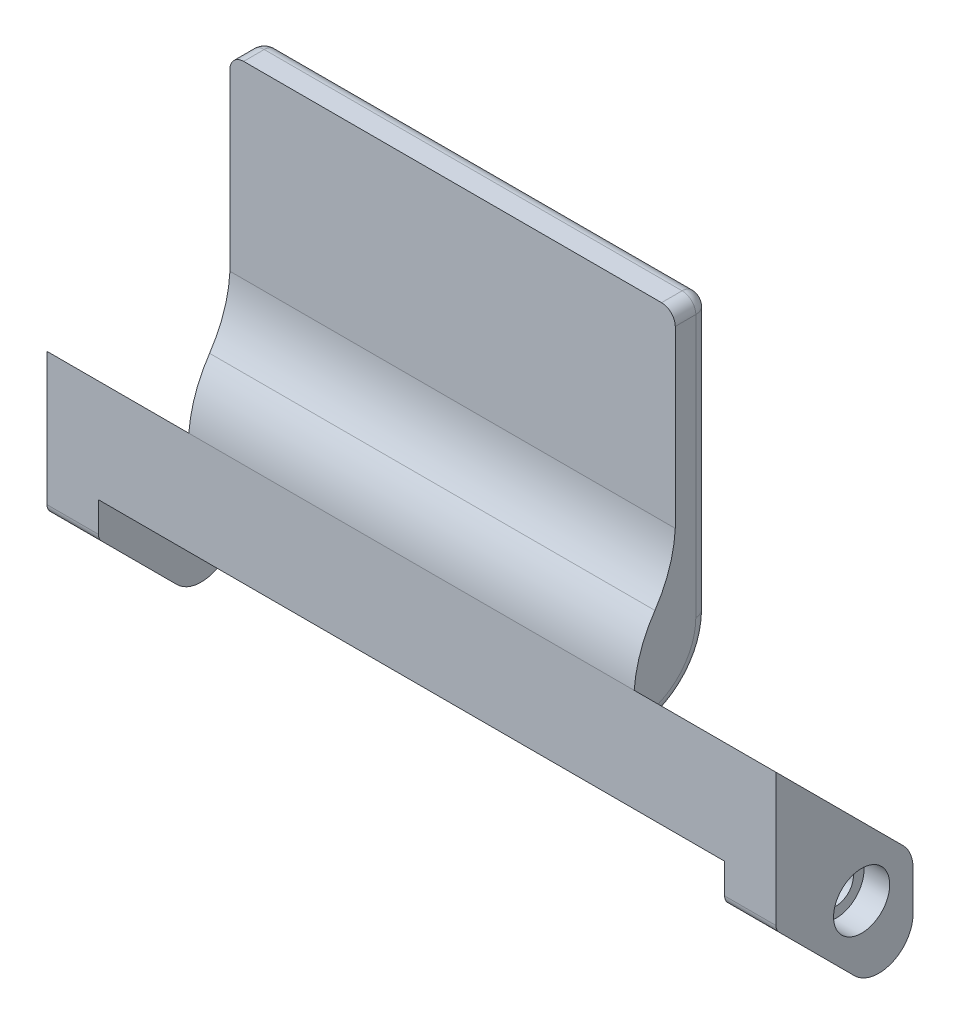
SolidWorks part; units mm, degrees
note: The reader was unsure of these and kept them because the rebuilt part matched: shared geometry of "Sketch8<3>".
ref_plane "Front Plane" through (0, 0, 0) normal (0, 0, 1) x (1, 0, 0)
ref_plane "Top Plane" through (0, 0, 0) normal (0, 1, 0) x (1, 0, 0)
ref_plane "Right Plane" through (0, 0, 0) normal (1, 0, 0) x (0, 0, -1)
ref_plane "Plane1" through (-53.2, 0, 0) normal (1, 0, 0) x (0, 0, -1)
sketch "Sketch1" plane through (0, 0, 0) normal (0, 0, 1) x (1, 0, 0)
  line L1 (32.5, -32.5) -> (-32.5, -32.5)
  line L2 (32.5, -32.5) -> (32.5, 32.5)
  line L3 (32.5, 32.5) -> (-32.5, 32.5)
  line L4 (-32.5, -32.5) -> (-32.5, 32.5)
  line L5 (32.5, -32.5) -> (-32.5, 32.5) construction
  line L6 (32.5, 32.5) -> (-32.5, -32.5) construction
  point P0 (0, 0)
  dimension "D1" = 65
  dimension "D2" = 65
extrude "Boss-Extrude1" add sketch "Sketch1" along normal blind 5
sketch "Sketch2" plane through (-53.2, 12.6, 0) normal (1, 0, 0) x (0, 1, 0)
  line L0 (-65.6, 5) -> (-65.6, -10)
  line L1 (-65.6, -10) -> (-58.1, -10)
  line L2 (-65.6, 5) -> (-45.1, 5)
  line L4 (-58.1, -10) -> (-58.1, 0)
  line L5 (-58.1, 0) -> (-45.1, 0)
  line L6 (-45.1, 0) -> (-45.1, 5)
  dimension "D1" = 15
  dimension "D2" = 45.5
  dimension "D3" = 7.5
sketch "Sketch4" plane through (-53.2, 0, 0) normal (-1, 0, 0) x (0, 0, 1)
  line L0 (5, -12.5) -> (-15, -32.5)
  line L1 (5, 32.5) -> (5, -32.5) construction
  line L2 (-15, -32.5) -> (-15, -52.5)
  line L3 (-15, -52.5) -> (5, -32.5)
  line L4 (0, -32.5) -> (5, -32.5) construction
  line L5 (5, -32.5) -> (5, -12.5)
  dimension "D1" = 45
  dimension "D2" = 20
  dimension "D3" = 20
extrude "Boss-Extrude3" add sketch "Sketch4" against normal blind 7.5
sketch "Sketch7" plane through (-53.2, 0, 0) normal (1, 0, 0) x (0, 0, -1)
  line L0 (-5, -32.5) -> (0, -32.5)
  line L1 (0, -32.5) -> (0, -17.5)
  line L2 (0, -32.5) -> (0, 32.5) construction
  line L3 (-5, -12.5) -> (15, -32.5) construction
  line L4 (0, -17.5) -> (-5, -12.5)
  line L5 (-5, -32.5) -> (-5, 32.5) construction
  line L6 (-5, -12.5) -> (-5, -32.5)
extrude "Boss-Extrude5" add sketch "Sketch7" along normal up to surface (85.7 mm away)
sketch "Sketch8" plane through (-53.2, 0, 0) normal (-1, 0, 0) x (0, 0, 1)
  line L0 (-15, -42.5) -> (5, -22.5) construction
  line L1 (-15, -32.5) -> (-15, -52.5) construction
  line L2 (5, -12.5) -> (5, -32.5) construction
  line L3 (-7.5, -35) -> (-15, -35) construction
  circle A0 centre (-7.5, -35) radius 2.55
  circle A1 centre (-7.5, -35) radius 4.1
  dimension "D1" = 5.1
  dimension "D2" = 8.2
  dimension "D3" = 7.5
extrude "Cut-Extrude4" cut sketch "Sketch8" against normal through all contours A0
extrude "Cut-Extrude5" cut sketch "Sketch8<3>" against normal blind 3.75
sketch "Sketch8<3>" plane through (-53.2, 0, 0) normal (-1, 0, 0) x (0, 0, 1) same geometry as "Sketch8"
mirror "Mirror5" about plane through (0, 0, 0) normal (1, 0, 0) of "Boss-Extrude3", "Boss-Extrude5"
sketch "Sketch9" plane through (53.2, 0, 0) normal (1, 0, 0) x (0, 0, -1)
  line L0 (0, -17.5) -> (-5, -12.5)
  line L1 (-5, -12.5) -> (-5, -32.5)
  line L5 (0, -17.5) -> (0, -32.5)
  line L6 (0, -32.5) -> (-5, -32.5)
  line L7 (-5, -32.5) -> (15, -52.5)
  line L8 (15, -52.5) -> (15, -32.5)
  line L9 (15, -32.5) -> (0, -17.5)
  line L12 (-5, -32.5) -> (15, -52.5)
  line L13 (15, -52.5) -> (15, -32.5)
  line L14 (15, -32.5) -> (0, -17.5)
  circle A0 centre (7.5, -35) radius 2.55
  dimension "D2" = 5.1
  dimension "D1" = 0
extrude "Boss-Extrude6" add sketch "Sketch9" against normal blind 7.5
sketch "Sketch10" plane through (53.2, 0, 0) normal (1, 0, 0) x (0, 0, -1)
  circle A0 centre (7.5, -35) radius 4.1
  dimension "D1" = 8.2
extrude "Cut-Extrude6" cut sketch "Sketch10" against normal blind 3.75
sketch "Sketch11" plane through (0, 0, 0) normal (1, 0, 0) x (0, 0, -1)
  line L0 (-5, -12.5) -> (-5, -32.5)
  line L1 (1, 4.9672) -> (1, 32.5)
  line L2 (1, 32.5) -> (6, 32.5)
  line L3 (6, 32.5) -> (6, 6.0076)
  line L5 (-5, 32.5) -> (0, 32.5) construction
  line L6 (-5, -32.5) -> (0, -32.5)
  line L7 (0, -32.5) -> (0, -17.5)
  line L8 (0, -17.5) -> (0, 32.5) construction
  arc A0 (1, 4.9672) -> (-1.9708, -3.9155) centre (-16.2173, 5.7874) cw
  arc A1 (-1.9708, -3.9155) -> (-5, -12.5) centre (12.7356, -13.9316) ccw
  arc A2 (6, 6.0076) -> (3.482, -5.2726) centre (-20.5257, 6.0076) cw
  arc A3 (3.482, -5.2726) -> (0, -17.5) centre (39.1922, -22.0513) ccw
  dimension "D2" = 17.2368
  dimension "D3" = 17.7933
  dimension "D4" = 26.5257
  dimension "D5" = 39.4555
  dimension "D1" = 5
  dimension "D6" = 8.5845
  dimension "D7" = 17.4672
  dimension "D8" = 12.2274
  dimension "D9" = 1
extrude "Boss-Extrude7" add sketch "Sketch11" along normal mid plane 65
sketch "Sketch13" plane through (0, 0, 0) normal (1, 0, 0) x (0, 0, -1)
  line L0 (1, 32.5) -> (-5, 32.5)
  line L1 (-5, 32.5) -> (-5, -12.5)
  line L6 (-5, -32.5) -> (0, -32.5)
  line L7 (0, -32.5) -> (0, -17.5)
  line L8 (6, 6.0076) -> (6, 32.5)
  line L9 (6, 32.5) -> (1, 32.5)
  line L10 (1, 32.5) -> (1, 4.9672)
  line L11 (-5, -12.5) -> (-5, -32.5)
  line L12 (-5, -32.5) -> (0, -32.5)
  line L13 (0, -32.5) -> (0, -17.5)
  line L14 (6, 6.0076) -> (6, 32.5)
  line L15 (6, 32.5) -> (1, 32.5)
  line L16 (1, 32.5) -> (1, 4.9672)
  line L17 (-5, -12.5) -> (-5, -32.5)
  arc A4 (3.482, -5.2726) -> (0, -17.5) centre (39.1922, -22.0513) ccw
  arc A5 (3.482, -5.2726) -> (6, 6.0076) centre (-20.5257, 6.0076) ccw
  arc A6 (-1.9708, -3.9155) -> (1, 4.9672) centre (-16.2173, 5.7874) ccw
  arc A7 (-1.9708, -3.9155) -> (-5, -12.5) centre (12.7356, -13.9316) ccw
  arc A8 (3.482, -5.2726) -> (0, -17.5) centre (39.1922, -22.0513) ccw
  arc A9 (3.482, -5.2726) -> (6, 6.0076) centre (-20.5257, 6.0076) ccw
  arc A10 (-1.9708, -3.9155) -> (1, 4.9672) centre (-16.2173, 5.7874) ccw
  arc A11 (-1.9708, -3.9155) -> (-5, -12.5) centre (12.7356, -13.9316) ccw
  dimension "D1" = 0
extrude "Cut-Extrude7" cut sketch "Sketch13" against normal mid plane 65 contours A11 A10 L16 L0 L1
fillet "Fillet1" radius 5 4 edges at (-49.45, -32.5, -15) (49.45, -32.5, -15) (-49.45, -52.5, -15) (49.45, -52.5, -15)
sketch "Sketch14" plane through (0, 0, 5) normal (0, 0, 1) x (1, 0, 0)
  line L1 (-45.7, -32.5) -> (45.7, -32.5) construction
  line L3 (0, 0) -> (0, -32.5) construction
  line L5 (-45.7, -32.5) -> (-45.7, -27.5)
  line L6 (-45.7, -27.5) -> (45.7, -27.5)
  line L7 (45.7, -27.5) -> (45.7, -32.5)
  line L8 (-45.7, -32.5) -> (45.7, -32.5)
  point P1 (2.3917, -32.5)
  point P6 (73.7438, -32.5)
  dimension "D1" = 5
extrude "Cut-Extrude8" cut sketch "Sketch14" against normal blind 10
fillet "Fillet2" radius 1.5 3 edges at (49.45, -32.5, 5) (-49.45, -32.5, 5) (0, -27.5, 0)
fillet "Fillet7" radius 2 2 edges at (-32.5, 32.5, -3.5) (32.5, 32.5, -3.5)
sketch "Sketch16" plane through (-32.5, 0, 0) normal (-1, 0, 0) x (0, 0, 1)
  line L0 (-6, 6.0076) -> (-6, -7.8214)
  line L1 (-6, 6.0076) -> (-6, 30.5) construction
  line L2 (-6, 6.0076) -> (-3.1128, 6.0076)
  line L3 (-3.1128, 6.0076) -> (2.8968, -14.6032)
  line L4 (0, -17.5) -> (5, -12.5) construction
  line L5 (2.8968, -14.6032) -> (0, -17.5)
  arc A0 (-6, -7.8214) -> (0, -17.5) centre (4.8063, -7.8214) ccw
  dimension "D1" = 10.8063
  dimension "D2" = 20.6108
  dimension "D3" = 2.8872
extrude "Boss-Extrude9" add sketch "Sketch16" against normal up to surface (65 mm away) up to face at (32.5, 4.0975, -1.3367)
fillet "Fillet9" radius 2 7 edges at (32.5, -13.5151, -4.3783) (-32.5, -13.5151, -4.3783) (-32.5, 11.3393, -6) (-31.9142, 31.9142, -6) (0, 32.5, -6) (31.9142, 31.9142, -6) (32.5, 11.3393, -6)
